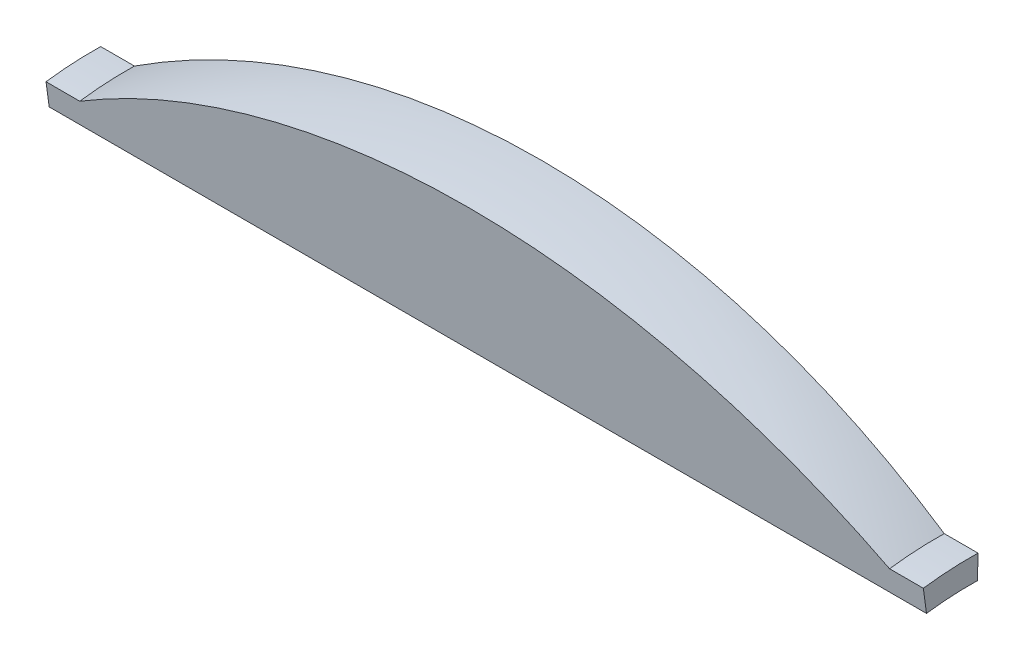
SolidWorks part; units mm, degrees
note: The reader was unsure of these and kept them because the rebuilt part matched: shared geometry of "Эскиз1<7>".
ref_plane "Спереди" through (0, 0, 0) normal (0, 0, 1) x (1, 0, 0)
ref_plane "Сверху" through (0, 0, 0) normal (0, 1, 0) x (1, 0, 0)
ref_plane "Справа" through (0, 0, 0) normal (1, 0, 0) x (0, 0, -1)
other "Configuration Table"
sketch "Эскиз1" plane through (0, 0, 0) normal (0, 0, 1) x (1, 0, 0)
  line L1 (0, 0) -> (0, 70)
  line L2 (0, 70) -> (-22.7031, 70) construction
  line L4 (-45, 48.8) -> (-45, 59.111)
  line L5 (-63.0381, 48.8) -> (0, 48.8)
  line L8 (-50, 0) -> (50, 0) construction
  line L9 (-45, 59.111) -> (0, 59.111)
  line L15 (-65, 52.5) -> (-65, 52.3)
  line L16 (-65, 52.3) -> (-60, 52.3)
  line L17 (-63.0381, 48.8) -> (-45, 48.8)
  line L18 (-65, 52.5) -> (-65, 48.8)
  line L19 (-65, 48.8) -> (-63.0381, 48.8)
  circle A0 centre (0, 0) radius 50 construction
  arc A3 (-60, 52.3) -> (0, 70) centre (0, -40.5449) cw
  arc A4 (-63.0381, 48.8) -> (0, 68.8) centre (0, -40.5449) cw
  dimension "D1" = 100
  dimension "D3" = 45
  dimension "D11" = 65
  dimension "D14" = 70
  dimension "D2" = 3.5
  dimension "D4" = 5
  dimension "D5" = 20
  dimension "D7" = 1.2
revolve "Повернуть1" add sketch "Эскиз1" angle 6.5 about L8
ref_plane "Плоскость2" through (0, 0, 0) normal (0, -0.0567, 0.9984) x (1, 0, 0)
revolve "Повернуть2" add sketch "Эскиз1<7>" angle 1.2 about L8
sketch "Эскиз1<7>" plane through (0, 0, 0) normal (0, 0, 1) x (1, 0, 0) same geometry as "Эскиз1"
mirror "Зеркальное отражение4" about plane through (0, 0, 0) normal (0, -0.0567, 0.9984) of "Повернуть2"
sketch "Эскиз6" plane through (0, 0, 0) normal (0, 1, 0) x (1, 0, 0)
  line L0 (0, -9.379) -> (0, 1.466) construction
  line L1 (0, -9.379) -> (0, 1.466)
  line L2 (-65, 1.0953) -> (-65, -7.0075) construction
  line L3 (-65, 1.0953) -> (-65, -7.0075)
  line L4 (-65, -2.9561) -> (-60, -2.9561) construction
  line L6 (-60, -7.0075) -> (-60, 1.0953) construction
  circle A0 centre (-60, -3.0352) radius 2.1
  dimension "D2" = 4.2
  dimension "D3" = 5
mirror "Зеркальное отражение5" of "Зеркальное отражение4", "Повернуть2", "Повернуть1"
fillet "Скругление4" radius 1 2 edges at (0, 68.3577, 7.7884) (0, 68.8, 0)
ref_plane "Плоскость4" through (0, 48.8, 0) normal (0, -1, 0) x (-1, 0, 0)
ref_plane "Плоскость5" through (-60, 0, 0) normal (-1, 0, 0) x (0, 0, 1)
sketch "Эскиз11" plane through (-60, 0, 0) normal (-1, 0, 0) x (0, 0, 1)
  line L0 (2.7666, 48.7215) -> (2.965, 52.2159) construction
  line L1 (-1.0953, 52.2885) -> (-1.022, 48.7893)
  line L2 (6.5385, 48.36) -> (7.0075, 51.8284)
  arc A0 (6.5385, 48.36) -> (-1.022, 48.7893) centre (0, 0) ccw construction
  arc A1 (7.0075, 51.8284) -> (-1.0953, 52.2885) centre (0, 0) ccw construction
  arc A2 (7.0075, 51.8284) -> (6.5385, 48.36) centre (5.8135, 50.2239) cw
  arc A3 (-1.0953, 52.2885) -> (-1.022, 48.7893) centre (-0.0906, 50.5592) ccw
  point P16 (7.7955, 49.956)
  dimension "D1" = 2
  dimension "D2" = 2
sketch "Эскиз12" plane through (0, 0, 0) normal (0, -0.0209, -0.9998) x (-1, 0, 0)
  line L0 (-60, 52.3) -> (-60, 48.8) construction
  line L2 (-60, 52.3) -> (-50, 52.3)
  line L3 (-60, 52.3) -> (-60, 48.8)
  line L4 (-60, 48.8) -> (-50, 48.8)
  line L5 (-65, 48.8) -> (65, 48.8)
  line L6 (65, 48.8) -> (65, 52.3)
  line L7 (65, 52.3) -> (60, 52.3)
  line L8 (-60, 52.3) -> (-65, 52.3)
  line L9 (-65, 52.3) -> (-65, 48.8)
  line L10 (-60, 48.8) -> (65, 48.8)
  line L15 (-50, 52.3) -> (-50, 48.8)
  arc A1 (60, 52.3) -> (-60, 52.3) centre (0, -40.5449) ccw
  dimension "D2" = 3.5
  dimension "D3" = 10
  dimension "D1" = 0
sketch "Эскиз13" plane through (0, 0, 0) normal (0, 0, 1) x (1, 0, 0)
  line L0 (0, 0) -> (-72.8834, 0) construction
